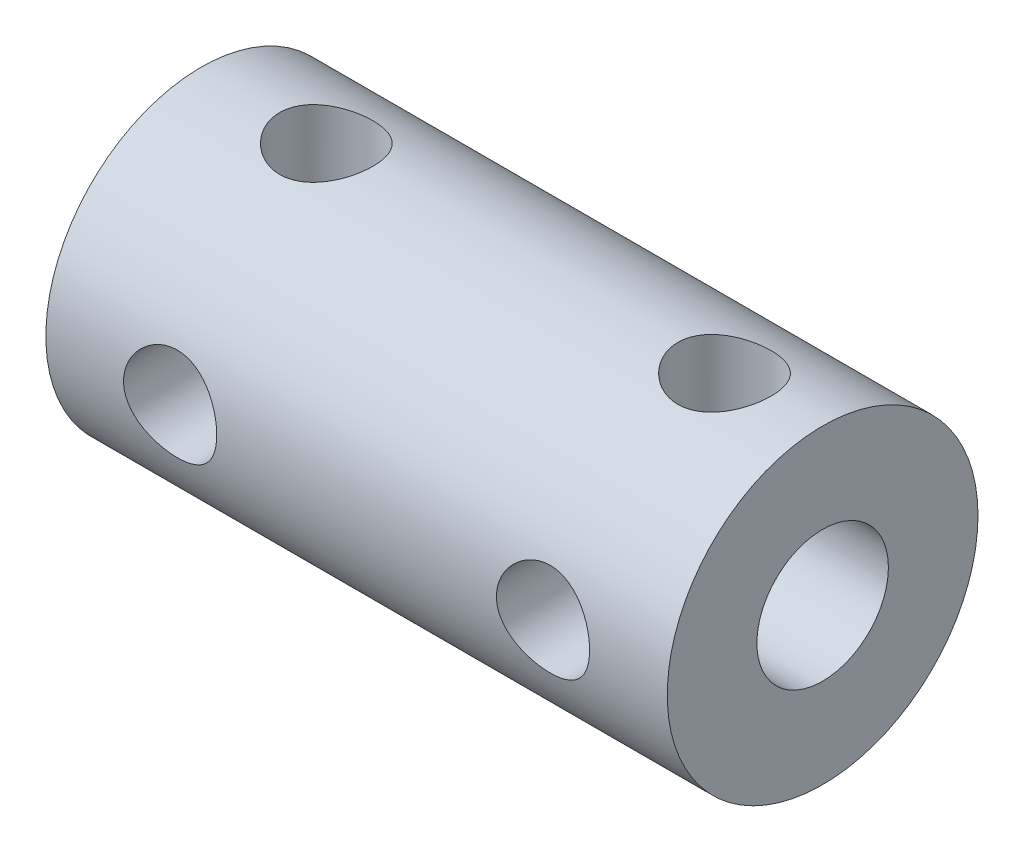
SolidWorks part; units mm, degrees
ref_plane "Alzado" through (0, 0, 0) normal (0, 0, 1) x (1, 0, 0)
ref_plane "Planta" through (0, 0, 0) normal (0, 1, 0) x (1, 0, 0)
ref_plane "Vista lateral" through (0, 0, 0) normal (1, 0, 0) x (0, 0, -1)
sketch "Croquis1" plane through (0, 0, 0) normal (1, 0, 0) x (0, 0, -1)
  circle A0 centre (0, 0) radius 7.5
  circle A1 centre (0, 0) radius 3.8779
  dimension "D1" = 15
extrude "Saliente-Extruir1" add sketch "Croquis1" along normal blind 15
sketch "Croquis3" plane through (15, 0, 0) normal (1, 0, 0) x (0, 0, -1)
  circle A0 centre (0, 0) radius 7.5
  circle A1 centre (0, 0) radius 3.175
extrude "Saliente-Extruir2" add sketch "Croquis3" along normal blind 15
hole_wizard "Taladro de margen para M41" positions "Croquis3D1" profile "Croquis5" hole size "M4" standard "Ansi Metric"
sketch3d "Croquis3D1"
  point P0 (6.0418, 7.5, 0)
  point P2 (25.2621, 7.5, 0)
  point P4 (6, 0, 7.5)
  point P6 (24, 0, 7.5)
  point P9 (-116.474, 0, -29.182)
  dimension "D1" = 6
  dimension "D2" = 6
sketch "Croquis5" plane through (6.0418, 7.5, 0) normal (1, 0, 0) x (0, 0, 1)
  line L0 (0, 0) -> (0, 8.8519)
  line L1 (0, 8.8519) -> (2.25, 7.5)
  line L2 (2.25, 7.5) -> (2.25, 0)
  line L5 (2.25, 0) -> (0, 0)
  line L10 (0, 8.8519) -> (-2.25, 7.5) construction
  line L11 (0, -6.35) -> (0, 107.95) construction
  dimension "Diámetro de taladro" = 4.5
  dimension "Profundidad de taladro" = 7.5
  dimension "Ángulo de perforador" = 118
